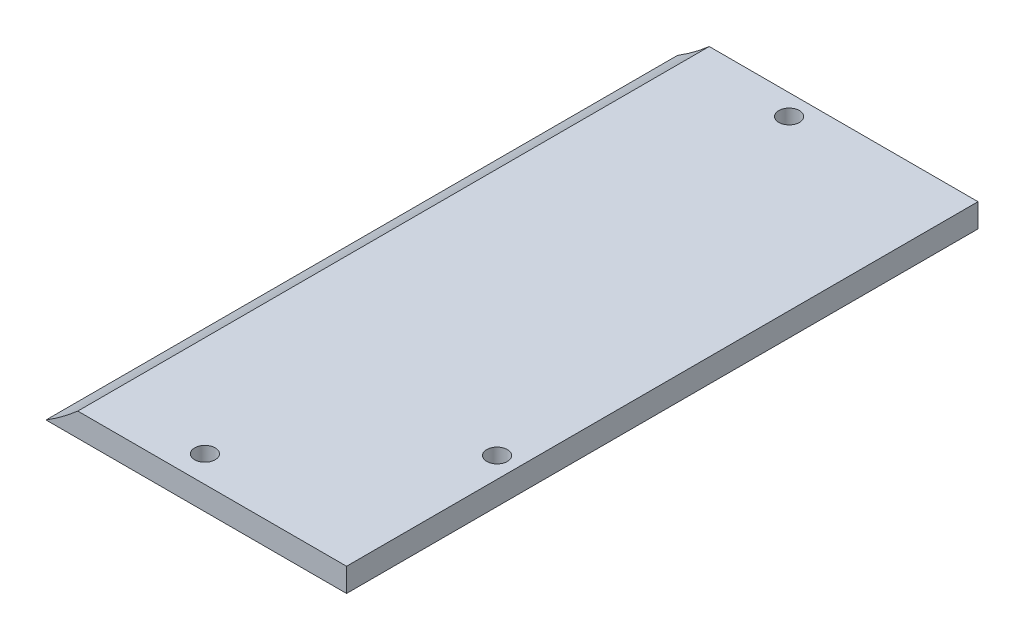
SolidWorks part; units mm, degrees
material "Acrylic (Medium-high impact)"
ref_plane "Front Plane" through (0, 0, 0) normal (0, 0, 1) x (1, 0, 0)
ref_plane "Top Plane" through (0, 0, 0) normal (0, 1, 0) x (1, 0, 0)
ref_plane "Right Plane" through (0, 0, 0) normal (1, 0, 0) x (0, 0, -1)
ref_axis "Axis1" through (0, 0, -5.35) along (0, 0, 1)
sketch "Sketch1" plane through (0, 0, 0) normal (0, 0, 1) x (1, 0, 0)
  circle A0 centre (0, 0) radius 38
  circle A1 centre (0, 0) radius 40
  dimension "D1" = 76
  dimension "D2" = 2
extrude "Boss-Extrude1" add sketch "Sketch1" along normal blind 200
ref_plane "Plane1" through (0, 0, 180) normal (0, 0, 1) x (1, 0, 0)
sketch "Sketch2" plane through (0, 0, 180) normal (0, 0, 1) x (1, 0, 0)
  circle A0 centre (0, 0) radius 40 construction
  circle A1 centre (0, 0) radius 40
extrude "Boss-Extrude2" add sketch "Sketch2" along normal blind 2
sketch "Sketch3" plane through (0, 0, 0) normal (0, 0, -1) x (-1, 0, 0)
  line L0 (-21.0713, -34) -> (-72, -34)
  line L1 (-72, -34) -> (-72, -30)
  line L2 (-72, -30) -> (-26.4575, -30)
  line L3 (-21.0713, 34) -> (-72, 34)
  line L4 (-72, 30) -> (-26.4575, 30)
  line L5 (-72, 34) -> (-72, 30)
  line L6 (-40, -15.2942) -> (-40, 13.2229) construction
  line L8 (0, 0) -> (-59.0266, 0) construction
  circle A1 centre (0, 0) radius 40 construction
  arc A2 (-21.0713, 34) -> (-26.4575, 30) centre (0, 0) ccw
  arc A3 (-26.4575, -30) -> (-21.0713, -34) centre (0, 0) ccw
  dimension "D1" = 60
  dimension "D2" = 4
  dimension "D3" = 32
extrude "Boss-Extrude3" add sketch "Sketch3" against normal blind 107
sketch "Sketch4" plane through (0, 0, 107) normal (0, 0, 1) x (1, 0, 0)
  line L2 (72, -34) -> (21.0713, -34) construction
  line L3 (21.0713, 34) -> (72, 34) construction
  line L4 (72, -34) -> (21.0713, -34)
  line L5 (21.0713, 34) -> (72, 34)
  line L6 (72, -34) -> (72, 34)
  circle A0 centre (0, 0) radius 40 construction
  arc A2 (21.0713, -34) -> (21.0713, 34) centre (0, 0) ccw
extrude "Boss-Extrude4" add sketch "Sketch4" along normal blind 2
sketch "Sketch5" plane through (0, 34, 0) normal (0, 1, 0) x (1, 0, 0)
  circle A5 centre (43.5, -102.5) radius 1.75 construction
  circle A6 centre (43.5, -102.5) radius 1.75
  circle A7 centre (43.5, -3.5) radius 1.75 construction
  circle A8 centre (43.5, -3.5) radius 1.75
  circle A9 centre (68.5, -78) radius 1.75 construction
  circle A10 centre (68.5, -78) radius 1.75
extrude "Cut-Extrude1" cut sketch "Sketch5" against normal through all
ref_plane "Plane2" through (0, 0, 0) normal (-0.7071, 0.7071, 0) x (0, 0, 1)
sketch "Sketch6" plane through (0, 0, 0) normal (-0.7071, 0.7071, 0) x (0, 0, 1)
  line L0 (200, -40) -> (200, 40) construction
  line L1 (200, -40) -> (200, 40) construction
  circle A0 centre (187, 0) radius 4
  dimension "D1" = 8
  dimension "D2" = 13
extrude "Cut-Extrude2" cut sketch "Sketch6" against normal up to next and the other way up to next
pattern_circular "CirPattern1" count 2 every 90 about axis through (0, 0, -5.35) along (0, 0, 1) of "Cut-Extrude2"
ref_plane "Plane3" through (-54, 0, 0) normal (1, 0, 0) x (0, 0, -1)
sketch "Sketch7" plane through (-54, 0, 0) normal (1, 0, 0) x (0, 0, -1)
  line L0 (0, 0) -> (-33.0452, 0) construction
  line L1 (-14, -11) -> (0, -11)
  line L2 (-14, -11) -> (-14, -13)
  line L3 (-14, -13) -> (0, -13)
  line L4 (0, -11) -> (0, -13)
  line L5 (0, -40) -> (0, 40) construction
  line L6 (0, 11) -> (0, 13)
  line L7 (-14, 13) -> (0, 13)
  line L8 (-14, 11) -> (-14, 13)
  line L9 (-14, 11) -> (0, 11)
  dimension "D1" = 2
  dimension "D2" = 14
  dimension "D3" = 22
extrude "Boss-Extrude5" add sketch "Sketch7" along normal up to surface (15.5422 mm away) up to face at (25.3934, 30.9059, 187.8976)
sketch "Sketch8" plane through (0, -13, 0) normal (0, -1, 0) x (1, 0, 0)
  line L6 (-37.8286, 14) -> (-37.8286, 0) construction
  line L7 (-37.8286, 0) -> (-54, 0) construction
  circle A0 centre (-49.7703, 5.0088) radius 1.75
  dimension "D3" = 3.5
  dimension "D1" = 11.9417
  dimension "D2" = 5.0088
extrude "Cut-Extrude3" cut sketch "Sketch8" against normal up to surface (26 mm away) up to face at (-45.9143, 13, 7)
fillet "Fillet1" radius 3 4 edges at (-54, 12, 0) (-54, -12, 0) (-54, -12, 14) (-54, 12, 14)
sketch "Sketch9" plane through (0, 11, 0) normal (0, -1, 0) x (1, 0, 0)
  circle A0 centre (-43.7703, 7.0088) radius 0.25
  circle A1 centre (-49.7703, 5.0088) radius 1.75 construction
  dimension "D1" = 6
  dimension "D2" = 2
  dimension "D3" = 0.5
extrude "Cut-Extrude4" cut sketch "Sketch9" against normal up to next
sketch "Sketch10" plane through (0, 0, 0) normal (0, 0, -1) x (-1, 0, 0)
  line L0 (-10, 38.7298) -> (-10, 36.6606)
  line L2 (10, 38.7298) -> (10, 36.6606)
  line L3 (-10, -36.6606) -> (-10, -38.7298)
  line L4 (10, -36.6606) -> (10, -38.7298)
  line L5 (-10, 36.6606) -> (10, 36.6606) construction
  line L6 (0, 36.6606) -> (0, 0) construction
  circle A0 centre (0, 0) radius 38 construction
  arc A1 (37.8286, 13) -> (-21.0713, 34) centre (0, 0) ccw construction
  arc A2 (-10, -36.6606) -> (10, -36.6606) centre (0, 0) ccw
  arc A3 (37.8286, 13) -> (-10, 38.7298) centre (0, 0) ccw
  arc A4 (10, 36.6606) -> (-10, 36.6606) centre (0, 0) ccw
  arc A5 (-21.0713, -34) -> (37.8286, -13) centre (0, 0) ccw construction
  arc A6 (-10, -38.7298) -> (37.8286, -13) centre (0, 0) ccw
  arc M9 (37.8286, 13) -> (-21.0713, 34) centre (0, 0) ccw
  arc M17 (-21.0713, -34) -> (37.8286, -13) centre (0, 0) ccw
  circle M22 centre (0, 0) radius 38
  dimension "D1" = 20
extrude "Boss-Extrude6" add sketch "Sketch10" along normal blind 2 contours L4 L3 M22 M17 | L2 L0 M9 M22 region at (0, 38.5641, 0) region at (0, -38.5641, 0)
sketch "Sketch11" plane through (0, 0, 200) normal (0, 0, 1) x (1, 0, 0)
  line L0 (72, -30) -> (26.4575, -30)
  line L1 (26.4575, -30) -> (72, -30) construction
  line L2 (21.0713, 34) -> (72, 34)
  line L3 (72, -34) -> (72, 34)
  line L4 (72, 34) -> (21.0713, 34)
  line L5 (21.0713, -34) -> (72, -34)
  line L6 (72, -30) -> (72, 34)
  line L7 (72, 34) -> (21.0713, 34) construction
  circle A0 centre (0, 0) radius 40 construction
  arc A1 (-5.6938, 39.5927) -> (-18.3942, -35.5198) centre (-27.0897, 4.5805) ccw
  arc A2 (-5.6938, 39.5927) -> (21.0713, 34) centre (0, 0) cw
  arc A3 (21.0713, -34) -> (21.0713, 34) centre (0, 0) ccw
  arc A4 (-18.3942, -35.5198) -> (26.4575, -30) centre (0, 0) ccw
  dimension "D1" = 0
extrude "Cut-Extrude5" cut sketch "Sketch11" against normal up to next
sketch "Sketch12" plane through (0, 0, 109) normal (0, 0, 1) x (1, 0, 0)
  line L3 (72, -30) -> (26.4575, -30)
  line L4 (21.0713, -34) -> (72, -34)
  line L5 (72, -34) -> (72, -30)
  line L6 (72, -30) -> (26.4575, -30)
  line L7 (21.0713, -34) -> (72, -34)
  line L8 (72, -34) -> (72, -30)
  arc A1 (21.0713, -34) -> (26.4575, -30) centre (0, 0) ccw
  arc A2 (21.0713, -34) -> (26.4575, -30) centre (0, 0) ccw
  dimension "D1" = 0
extrude "Cut-Extrude6" cut sketch "Sketch12" against normal blind 2
